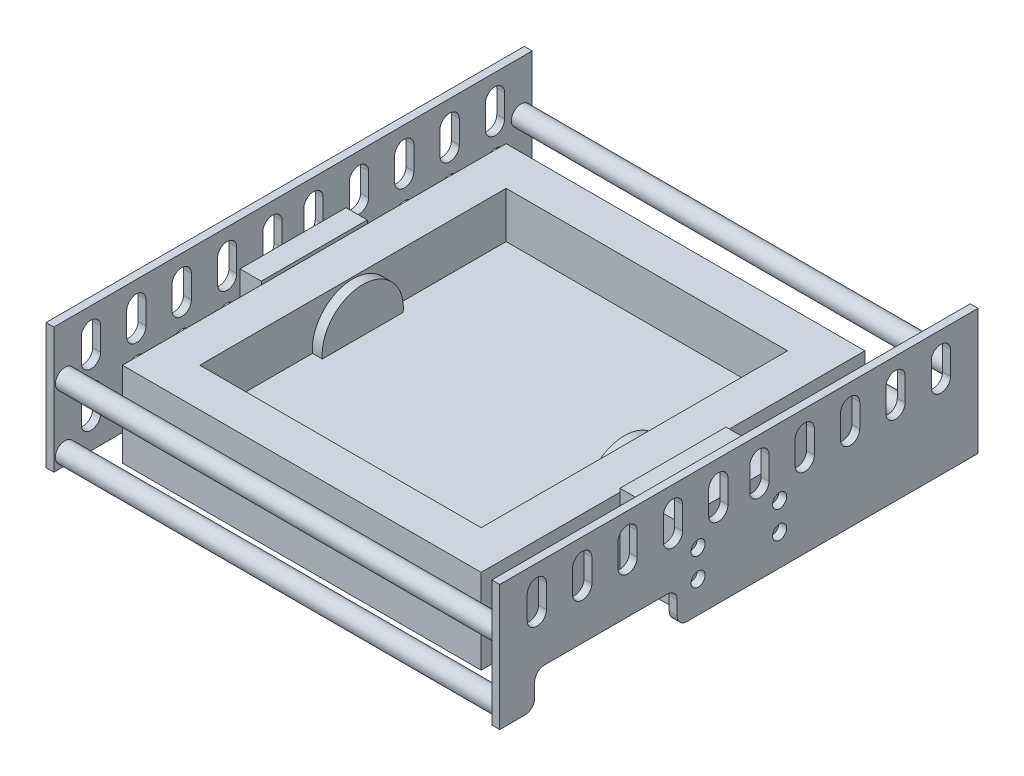
SolidWorks part; units mm, degrees
ref_plane "Front Plane" through (0, 0, 0) normal (0, 0, 1) x (1, 0, 0)
ref_plane "Top Plane" through (0, 0, 0) normal (0, 1, 0) x (1, 0, 0)
ref_plane "Right Plane" through (0, 0, 0) normal (1, 0, 0) x (0, 0, -1)
sketch "Sketch1" plane through (0, 0, 0) normal (1, 0, 0) x (0, 0, -1)
  line L0 (0, 0) -> (0, -16.4338) construction
  line L1 (0, 0) -> (55.8004, 0) construction
  line L2 (0, -16.4338) -> (117.9322, -16.4338) construction
  line L3 (117.9322, -16.4338) -> (117.9322, 0) construction
  line L4 (-2.5019, -18.9357) -> (120.4341, -18.9357) construction
  line L5 (-2.5019, 2.5019) -> (120.4341, 2.5019) construction
  line L6 (-2.5019, 2.5019) -> (-2.5019, -18.9357) construction
  line L7 (120.4341, 2.5019) -> (120.4341, -18.9357) construction
  circle A0 centre (0, 0) radius 2.5019
  circle A1 centre (0, -16.4338) radius 2.5019
  circle A2 centre (117.9322, -16.4338) radius 2.5019
  circle A3 centre (117.9322, 0) radius 2.5019
  dimension "D2" = 5.0038
  dimension "D3" = 21.4376
  dimension "D4" = 122.936
extrude "Boss-Extrude1" add sketch "Sketch1" along normal blind 115.316
ref_plane "Plane1" through (12.7, 0, 0) normal (1, 0, 0) x (0, 0, -1)
sketch "Sketch5" plane through (0, 0, 0) normal (1, 0, 0) x (0, 0, -1)
  line L4 (0, 0) -> (117.9322, -16.4338) construction
  line L5 (58.9661, 12.954) -> (58.9661, -19.558) construction
  line L6 (4.2291, -14.9987) -> (4.2291, 9.7028) construction
  line L8 (6.7183, 1.27) -> (6.7183, 7.2136) construction
  line L10 (4.2291, 9.7028) -> (113.7031, 9.7028) construction
  line L15 (113.7031, -14.9987) -> (4.2291, -14.9987) construction
  line L20 (117.9322, 0) -> (0, -16.4338) construction
  line L29 (64.2747, 1.27) -> (64.2747, 7.2136) construction
  line L38 (66.7639, 1.27) -> (66.7639, 7.2136)
  line L45 (61.7855, 1.27) -> (61.7855, 7.2136)
  line L52 (64.2747, -12.5095) -> (64.2747, -6.5659) construction
  line L61 (66.7639, -12.5095) -> (66.7639, -6.5659)
  line L70 (61.7855, -12.5095) -> (61.7855, -6.5659)
  line L76 (-2.8829, -19.558) -> (120.8151, -19.558)
  line L77 (-2.8829, -19.558) -> (-2.8829, 12.954)
  line L78 (-2.8829, 12.954) -> (120.8151, 12.954)
  line L79 (120.8151, -19.558) -> (120.8151, 12.954)
  line L80 (76.0095, -12.5095) -> (76.0095, -6.5659) construction
  line L81 (78.4987, -12.5095) -> (78.4987, -6.5659)
  line L82 (4.2291, 1.27) -> (4.2291, 7.2136)
  line L83 (9.2075, 1.27) -> (9.2075, 7.2136)
  line L84 (4.2291, 9.7028) -> (9.2075, 9.7028) construction
  line L85 (9.2075, 9.7028) -> (9.2075, -1.2192) construction
  line L86 (9.2075, -1.2192) -> (4.2291, -1.2192) construction
  line L87 (4.2291, -1.2192) -> (4.2291, 9.7028) construction
  line L88 (18.4531, 1.27) -> (18.4531, 7.2136) construction
  line L89 (15.9639, 1.27) -> (15.9639, 7.2136)
  line L90 (20.9423, 1.27) -> (20.9423, 7.2136)
  line L91 (30.1879, 1.27) -> (30.1879, 7.2136) construction
  line L92 (27.6987, 1.27) -> (27.6987, 7.2136)
  line L93 (32.6771, 1.27) -> (32.6771, 7.2136)
  line L94 (41.9227, 1.27) -> (41.9227, 7.2136) construction
  line L95 (39.4335, 1.27) -> (39.4335, 7.2136)
  line L96 (44.4119, 1.27) -> (44.4119, 7.2136)
  line L97 (53.6575, 1.27) -> (53.6575, 7.2136) construction
  line L98 (51.1683, 1.27) -> (51.1683, 7.2136)
  line L99 (56.1467, 1.27) -> (56.1467, 7.2136)
  line L100 (18.4531, -12.5095) -> (18.4531, -6.5659) construction
  line L101 (15.9639, -12.5095) -> (15.9639, -6.5659)
  line L102 (20.9423, -12.5095) -> (20.9423, -6.5659)
  line L103 (30.1879, -12.5095) -> (30.1879, -6.5659) construction
  line L104 (27.6987, -12.5095) -> (27.6987, -6.5659)
  line L105 (32.6771, -12.5095) -> (32.6771, -6.5659)
  line L106 (41.9227, -12.5095) -> (41.9227, -6.5659) construction
  line L107 (39.4335, -12.5095) -> (39.4335, -6.5659)
  line L108 (44.4119, -12.5095) -> (44.4119, -6.5659)
  line L109 (53.6575, -12.5095) -> (53.6575, -6.5659) construction
  line L110 (51.1683, -12.5095) -> (51.1683, -6.5659)
  line L111 (56.1467, -12.5095) -> (56.1467, -6.5659)
  line L112 (6.7183, -12.5095) -> (6.7183, -6.5659) construction
  line L113 (4.2291, -12.5095) -> (4.2291, -6.5659)
  line L114 (9.2075, -12.5095) -> (9.2075, -6.5659)
  line L116 (73.5203, -12.5095) -> (73.5203, -6.5659)
  line L117 (113.7031, 9.7028) -> (113.7031, -14.9987) construction
  line L118 (76.0095, 1.27) -> (76.0095, 7.2136) construction
  line L119 (78.4987, 1.27) -> (78.4987, 7.2136)
  line L120 (73.5203, 1.27) -> (73.5203, 7.2136)
  line L121 (87.7443, 1.27) -> (87.7443, 7.2136) construction
  line L122 (90.2335, 1.27) -> (90.2335, 7.2136)
  line L123 (85.2551, 1.27) -> (85.2551, 7.2136)
  line L124 (87.7443, -12.5095) -> (87.7443, -6.5659) construction
  line L125 (90.2335, -12.5095) -> (90.2335, -6.5659)
  line L126 (85.2551, -12.5095) -> (85.2551, -6.5659)
  line L127 (99.4791, -12.5095) -> (99.4791, -6.5659) construction
  line L128 (101.9683, -12.5095) -> (101.9683, -6.5659)
  line L129 (96.9899, -12.5095) -> (96.9899, -6.5659)
  line L130 (99.4791, 1.27) -> (99.4791, 7.2136) construction
  line L131 (101.9683, 1.27) -> (101.9683, 7.2136)
  line L132 (96.9899, 1.27) -> (96.9899, 7.2136)
  line L133 (111.2139, 1.27) -> (111.2139, 7.2136) construction
  line L134 (113.7031, 1.27) -> (113.7031, 7.2136)
  line L135 (108.7247, 1.27) -> (108.7247, 7.2136)
  line L136 (111.2139, -12.5095) -> (111.2139, -6.5659) construction
  line L137 (113.7031, -12.5095) -> (113.7031, -6.5659)
  line L138 (108.7247, -12.5095) -> (108.7247, -6.5659)
  line L140 (-6.1459, 2.5019) -> (0, 2.5019) construction
  line L146 (46.609, -13.3223) -> (71.3232, -13.3223) construction
  line L147 (46.609, -13.3223) -> (46.609, -2.6162) construction
  line L148 (46.609, -2.6162) -> (71.3232, -2.6162) construction
  line L149 (71.3232, -13.3223) -> (71.3232, -2.6162) construction
  line L150 (46.609, -13.3223) -> (71.3232, -2.6162) construction
  line L151 (46.609, -2.6162) -> (71.3232, -13.3223) construction
  arc A40 (4.2291, 1.27) -> (9.2075, 1.27) centre (6.7183, 1.27) ccw
  arc A41 (9.2075, 7.2136) -> (4.2291, 7.2136) centre (6.7183, 7.2136) ccw
  arc A42 (15.9639, 1.27) -> (20.9423, 1.27) centre (18.4531, 1.27) ccw
  arc A43 (20.9423, 7.2136) -> (15.9639, 7.2136) centre (18.4531, 7.2136) ccw
  arc A44 (27.6987, 1.27) -> (32.6771, 1.27) centre (30.1879, 1.27) ccw
  arc A45 (32.6771, 7.2136) -> (27.6987, 7.2136) centre (30.1879, 7.2136) ccw
  arc A46 (39.4335, 1.27) -> (44.4119, 1.27) centre (41.9227, 1.27) ccw
  arc A47 (44.4119, 7.2136) -> (39.4335, 7.2136) centre (41.9227, 7.2136) ccw
  arc A48 (51.1683, 1.27) -> (56.1467, 1.27) centre (53.6575, 1.27) ccw
  arc A49 (56.1467, 7.2136) -> (51.1683, 7.2136) centre (53.6575, 7.2136) ccw
  arc A50 (15.9639, -12.5095) -> (20.9423, -12.5095) centre (18.4531, -12.5095) ccw
  arc A51 (20.9423, -6.5659) -> (15.9639, -6.5659) centre (18.4531, -6.5659) ccw
  arc A52 (27.6987, -12.5095) -> (32.6771, -12.5095) centre (30.1879, -12.5095) ccw
  arc A53 (32.6771, -6.5659) -> (27.6987, -6.5659) centre (30.1879, -6.5659) ccw
  arc A54 (39.4335, -12.5095) -> (44.4119, -12.5095) centre (41.9227, -12.5095) ccw
  arc A55 (44.4119, -6.5659) -> (39.4335, -6.5659) centre (41.9227, -6.5659) ccw
  arc A56 (51.1683, -12.5095) -> (56.1467, -12.5095) centre (53.6575, -12.5095) ccw
  arc A57 (56.1467, -6.5659) -> (51.1683, -6.5659) centre (53.6575, -6.5659) ccw
  arc A58 (4.2291, -12.5095) -> (9.2075, -12.5095) centre (6.7183, -12.5095) ccw
  arc A59 (9.2075, -6.5659) -> (4.2291, -6.5659) centre (6.7183, -6.5659) ccw
  circle A60 centre (0, 0) radius 2.5019 construction
  circle A61 centre (0, -16.4338) radius 2.5019 construction
  circle A62 centre (117.9322, 0) radius 2.5019 construction
  circle A63 centre (117.9322, -16.4338) radius 2.5019 construction
  arc A64 (66.7639, 1.27) -> (61.7855, 1.27) centre (64.2747, 1.27) cw
  arc A65 (61.7855, 7.2136) -> (66.7639, 7.2136) centre (64.2747, 7.2136) cw
  arc A66 (66.7639, -12.5095) -> (61.7855, -12.5095) centre (64.2747, -12.5095) cw
  arc A67 (61.7855, -6.5659) -> (66.7639, -6.5659) centre (64.2747, -6.5659) cw
  arc A68 (78.4987, -12.5095) -> (73.5203, -12.5095) centre (76.0095, -12.5095) cw
  arc A69 (73.5203, -6.5659) -> (78.4987, -6.5659) centre (76.0095, -6.5659) cw
  arc A70 (78.4987, 1.27) -> (73.5203, 1.27) centre (76.0095, 1.27) cw
  arc A71 (73.5203, 7.2136) -> (78.4987, 7.2136) centre (76.0095, 7.2136) cw
  arc A72 (90.2335, 1.27) -> (85.2551, 1.27) centre (87.7443, 1.27) cw
  arc A73 (85.2551, 7.2136) -> (90.2335, 7.2136) centre (87.7443, 7.2136) cw
  arc A74 (90.2335, -12.5095) -> (85.2551, -12.5095) centre (87.7443, -12.5095) cw
  arc A75 (85.2551, -6.5659) -> (90.2335, -6.5659) centre (87.7443, -6.5659) cw
  arc A76 (101.9683, -12.5095) -> (96.9899, -12.5095) centre (99.4791, -12.5095) cw
  arc A77 (96.9899, -6.5659) -> (101.9683, -6.5659) centre (99.4791, -6.5659) cw
  arc A78 (101.9683, 1.27) -> (96.9899, 1.27) centre (99.4791, 1.27) cw
  arc A79 (96.9899, 7.2136) -> (101.9683, 7.2136) centre (99.4791, 7.2136) cw
  arc A80 (113.7031, 1.27) -> (108.7247, 1.27) centre (111.2139, 1.27) cw
  arc A81 (108.7247, 7.2136) -> (113.7031, 7.2136) centre (111.2139, 7.2136) cw
  arc A82 (113.7031, -12.5095) -> (108.7247, -12.5095) centre (111.2139, -12.5095) cw
  arc A83 (108.7247, -6.5659) -> (113.7031, -6.5659) centre (111.2139, -6.5659) cw
  circle A84 centre (48.4314, -4.4386) radius 1.8225
  circle A85 centre (48.4314, -11.4998) radius 1.8225
  circle A86 centre (69.5007, -4.4386) radius 1.8224
  circle A87 centre (69.5007, -11.4998) radius 1.8224
  point P15 (58.9661, -8.2169)
  point P19 (64.2747, 4.2418)
  point P26 (64.2747, -9.5377)
  point P36 (76.0095, -9.5377)
  point P43 (76.0095, 4.2418)
  point P50 (87.7443, 4.2418)
  point P57 (87.7443, -9.5377)
  point P64 (99.4791, -9.5377)
  point P71 (99.4791, 4.2418)
  point P78 (111.2139, 4.2418)
  point P88 (111.2139, -9.5377)
  point P100 (58.9661, -7.9692)
  point P166 (6.7183, 4.2418)
  point P180 (18.4531, 4.2418)
  point P187 (30.1879, 4.2418)
  point P194 (41.9227, 4.2418)
  point P201 (53.6575, 4.2418)
  point P208 (18.4531, -9.5377)
  point P215 (30.1879, -9.5377)
  point P222 (41.9227, -9.5377)
  point P229 (53.6575, -9.5377)
  point P236 (6.7183, -9.5377)
  dimension "D3" = 123.698
  dimension "D8" = 3.6449
  dimension "D4" = 10.4521
  dimension "D5" = 24.7142
  dimension "D6" = 10.7061
  dimension "D11" = 32.512
  dimension "D13" = 3.2512
  dimension "D14" = 7.112
  dimension "D15" = 4.9784
  dimension "D16" = 10.922
  dimension "D19" = 13.7795
  dimension "D20" = 11.7348
  dimension "D7" = 6.2357
  dimension "D17" = 5
  dimension "D18" = 2
extrude "Boss-Extrude3" add sketch "Sketch5" along normal blind 2.032
ref_plane "Plane2" through (115.316, 0, 0) normal (1, 0, 0) x (0, 0, -1)
sketch "Sketch6" plane through (115.316, 0, 0) normal (1, 0, 0) x (0, 0, -1)
  line L0 (120.8151, 12.954) -> (-2.8829, 12.954) construction
  line L1 (-2.8829, -19.558) -> (3.6195, -19.558)
  line L2 (-2.8829, -19.558) -> (-2.8829, 12.954)
  line L3 (-2.8829, 12.954) -> (120.8151, 12.954)
  line L4 (120.8151, -19.558) -> (120.8151, 12.954)
  line L5 (-2.8829, -19.558) -> (120.8151, 12.954) construction
  line L6 (-2.8829, 12.954) -> (120.8151, -19.558) construction
  line L7 (-2.8829, 12.954) -> (-2.8829, -19.558) construction
  line L8 (6.1595, -17.018) -> (6.1595, -13.4112)
  line L9 (8.6995, -10.8712) -> (40.4495, -10.8712)
  line L10 (42.9895, -13.4112) -> (42.9895, -17.018)
  line L11 (45.5295, -19.558) -> (120.8151, -19.558)
  line L88 (15.9639, 7.2136) -> (15.9639, 1.27)
  line L89 (20.9423, 1.27) -> (20.9423, 7.2136)
  line L90 (9.2075, 1.27) -> (9.2075, 7.2136)
  line L91 (4.2291, 7.2136) -> (4.2291, 1.27)
  line L92 (9.2075, 1.27) -> (9.2075, 7.2136)
  line L93 (4.2291, 7.2136) -> (4.2291, 1.27)
  line L94 (27.6987, 7.2136) -> (27.6987, 1.27)
  line L95 (32.6771, 1.27) -> (32.6771, 7.2136)
  line L96 (39.4335, 7.2136) -> (39.4335, 1.27)
  line L97 (44.4119, 1.27) -> (44.4119, 7.2136)
  line L98 (51.1683, 7.2136) -> (51.1683, 1.27)
  line L99 (56.1467, 1.27) -> (56.1467, 7.2136)
  line L100 (15.9639, 7.2136) -> (15.9639, 1.27) construction
  line L101 (58.9661, 12.954) -> (58.9661, -19.558) construction
  line L102 (61.7855, 1.27) -> (61.7855, 7.2136)
  line L103 (66.7639, 7.2136) -> (66.7639, 1.27)
  line L104 (73.5203, 1.27) -> (73.5203, 7.2136)
  line L105 (78.4987, 7.2136) -> (78.4987, 1.27)
  line L106 (85.2551, 1.27) -> (85.2551, 7.2136)
  line L107 (90.2335, 7.2136) -> (90.2335, 1.27)
  line L108 (96.9899, 1.27) -> (96.9899, 7.2136)
  line L109 (101.9683, 7.2136) -> (101.9683, 1.27)
  line L110 (113.7031, 7.2136) -> (113.7031, 1.27)
  line L111 (108.7247, 1.27) -> (108.7247, 7.2136)
  circle A5 centre (48.4314, -4.4386) radius 1.8225
  circle A6 centre (48.4314, -4.4386) radius 1.8225 construction
  circle A7 centre (69.5007, -4.4386) radius 1.8224
  circle A8 centre (69.5007, -11.4998) radius 1.8224
  circle A9 centre (48.4314, -11.4998) radius 1.8225
  circle A10 centre (48.4314, -11.4998) radius 1.8225 construction
  circle A11 centre (69.5007, -11.4998) radius 1.8225 construction
  circle A12 centre (69.5007, -4.4386) radius 1.8225 construction
  arc A70 (20.9423, 7.2136) -> (15.9639, 7.2136) centre (18.4531, 7.2136) ccw
  arc A71 (15.9639, 1.27) -> (20.9423, 1.27) centre (18.4531, 1.27) ccw
  arc A72 (4.2291, 1.27) -> (9.2075, 1.27) centre (6.7183, 1.27) ccw
  arc A73 (9.2075, 7.2136) -> (4.2291, 7.2136) centre (6.7183, 7.2136) ccw
  arc A74 (4.2291, 1.27) -> (9.2075, 1.27) centre (6.7183, 1.27) ccw
  arc A75 (9.2075, 7.2136) -> (4.2291, 7.2136) centre (6.7183, 7.2136) ccw
  arc A76 (32.6771, 7.2136) -> (27.6987, 7.2136) centre (30.1879, 7.2136) ccw
  arc A77 (27.6987, 1.27) -> (32.6771, 1.27) centre (30.1879, 1.27) ccw
  arc A78 (44.4119, 7.2136) -> (39.4335, 7.2136) centre (41.9227, 7.2136) ccw
  arc A79 (39.4335, 1.27) -> (44.4119, 1.27) centre (41.9227, 1.27) ccw
  arc A80 (56.1467, 7.2136) -> (51.1683, 7.2136) centre (53.6575, 7.2136) ccw
  arc A81 (51.1683, 1.27) -> (56.1467, 1.27) centre (53.6575, 1.27) ccw
  arc A82 (61.7855, 7.2136) -> (66.7639, 7.2136) centre (64.2747, 7.2136) cw
  arc A83 (66.7639, 1.27) -> (61.7855, 1.27) centre (64.2747, 1.27) cw
  arc A84 (73.5203, 7.2136) -> (78.4987, 7.2136) centre (76.0095, 7.2136) cw
  arc A85 (78.4987, 1.27) -> (73.5203, 1.27) centre (76.0095, 1.27) cw
  arc A86 (85.2551, 7.2136) -> (90.2335, 7.2136) centre (87.7443, 7.2136) cw
  arc A87 (90.2335, 1.27) -> (85.2551, 1.27) centre (87.7443, 1.27) cw
  arc A88 (96.9899, 7.2136) -> (101.9683, 7.2136) centre (99.4791, 7.2136) cw
  arc A89 (101.9683, 1.27) -> (96.9899, 1.27) centre (99.4791, 1.27) cw
  arc A90 (108.7247, 7.2136) -> (113.7031, 7.2136) centre (111.2139, 7.2136) cw
  arc A91 (113.7031, 1.27) -> (108.7247, 1.27) centre (111.2139, 1.27) cw
  arc A92 (42.9895, -17.018) -> (45.5295, -19.558) centre (45.5295, -17.018) ccw
  arc A93 (40.4495, -10.8712) -> (42.9895, -13.4112) centre (40.4495, -13.4112) cw
  arc A94 (6.1595, -13.4112) -> (8.6995, -10.8712) centre (8.6995, -13.4112) cw
  arc A95 (6.1595, -17.018) -> (3.6195, -19.558) centre (3.6195, -17.018) cw
  point P0 (58.9661, -3.302)
  point P79 (42.9895, -19.558)
  point P82 (42.9895, -10.8712)
  point P85 (6.1595, -10.8712)
  point P88 (6.1595, -19.558)
  dimension "D6" = 2.54
  dimension "D3" = 8.6868
  dimension "D4" = 36.83
  dimension "D5" = 9.0424
  dimension "D1" = 0
  dimension "D2" = 5
extrude "Boss-Extrude4" add sketch "Sketch6" along normal blind 2.032 separate body
sketch "Sketch7" plane through (115.316, 0, 0) normal (-1, 0, 0) x (0, 0, 1)
  line L0 (-69.5007, -4.4386) -> (-48.4314, -11.4998) construction
  line L1 (-72.6758, -17.8498) -> (-45.2564, -17.8498)
  line L2 (-72.6758, -17.8498) -> (-72.6758, 1.9114)
  line L3 (-72.6758, 1.9114) -> (-45.2564, 1.9114)
  line L4 (-45.2564, -17.8498) -> (-45.2564, 1.9114)
  line L5 (-72.6758, -17.8498) -> (-45.2564, 1.9114) construction
  line L6 (-72.6758, 1.9114) -> (-45.2564, -17.8498) construction
  line L7 (-69.5007, -4.4386) -> (-69.5007, 1.9114) construction
  line L8 (-69.5007, -4.4386) -> (-72.6758, -4.4386) construction
  point P0 (-58.9661, -7.9692)
  point P9 (-58.9661, -7.9692)
  dimension "D1" = 6.35
  dimension "D2" = 3.175
extrude "Boss-Extrude5" add sketch "Sketch7" along normal blind 15
sketch "Sketch8" plane through (2.032, 0, 0) normal (1, 0, 0) x (0, 0, -1)
  line L0 (48.4314, -4.4386) -> (69.5007, -11.4998) construction
  line L1 (45.2564, -17.8498) -> (72.6757, -17.8498)
  line L2 (45.2564, -17.8498) -> (45.2564, 1.9114)
  line L3 (45.2564, 1.9114) -> (72.6757, 1.9114)
  line L4 (72.6757, -17.8498) -> (72.6757, 1.9114)
  line L5 (45.2564, -17.8498) -> (72.6757, 1.9114) construction
  line L6 (45.2564, 1.9114) -> (72.6757, -17.8498) construction
  line L7 (48.4314, -4.4386) -> (48.4314, 1.9114) construction
  line L8 (48.4314, -4.4386) -> (45.2564, -4.4386) construction
  point P0 (58.9661, -7.9692)
  dimension "D1" = 6.35
  dimension "D2" = 3.175
extrude "Boss-Extrude6" add sketch "Sketch8" along normal blind 5.5
ref_plane "Plane3" through (0, -20.8915, 0) normal (0, -1, 0) x (-1, 0, 0)
sketch "Sketch9" plane through (0, -20.8915, 0) normal (0, -1, 0) x (-1, 0, 0)
  line L0 (-7.532, 72.6757) -> (-7.532, 45.2564) construction
  line L1 (-7.532, 9.3472) -> (-100.316, 9.3472)
  line L2 (-7.532, 9.3472) -> (-7.532, 108.585)
  line L3 (-7.532, 108.585) -> (-100.316, 108.585)
  line L4 (-100.316, 9.3472) -> (-100.316, 108.585)
  line L5 (-7.532, 9.3472) -> (-100.316, 108.585) construction
  line L6 (-7.532, 108.585) -> (-100.316, 9.3472) construction
  line L7 (-100.316, 45.2564) -> (-100.316, 72.6758) construction
  line L8 (-115.316, 115.4303) -> (-2.032, 115.4303) construction
  line L9 (-7.532, 108.585) -> (-7.532, 115.4303) construction
  line L10 (-7.532, 9.3472) -> (-7.532, 2.5019) construction
  line L11 (-2.032, 2.5019) -> (-115.316, 2.5019) construction
  point P0 (-53.924, 58.9661)
  dimension "D1" = 6.8453
extrude "Boss-Extrude7" add sketch "Sketch9" against normal blind 21.9329 separate body contours L1 L4 L3 L2
sketch "Sketch10" plane through (7.532, 0, 0) normal (-1, 0, 0) x (0, 0, 1)
  line L0 (-108.585, 1.0414) -> (-9.3472, -20.8915) construction
  circle A0 centre (-58.9661, -9.925) radius 0.508
  dimension "D1" = 1.016
extrude "Cut-Extrude1" cut sketch "Sketch10" against normal blind 2.54 and the other way blind 2.54
sketch "Sketch11" plane through (100.316, 0, 0) normal (1, 0, 0) x (0, 0, -1)
  line L0 (9.3472, 1.0414) -> (108.585, -20.8915) construction
  circle A0 centre (58.9661, -9.9251) radius 0.508
  dimension "D1" = 1.016
extrude "Cut-Extrude2" cut sketch "Sketch11" against normal blind 2.54 and the other way blind 2.54
shell "Shell1" thickness 10 removed face at (53.924, 1.0414, -58.9661)
equation "\"x\"= 5cm"
